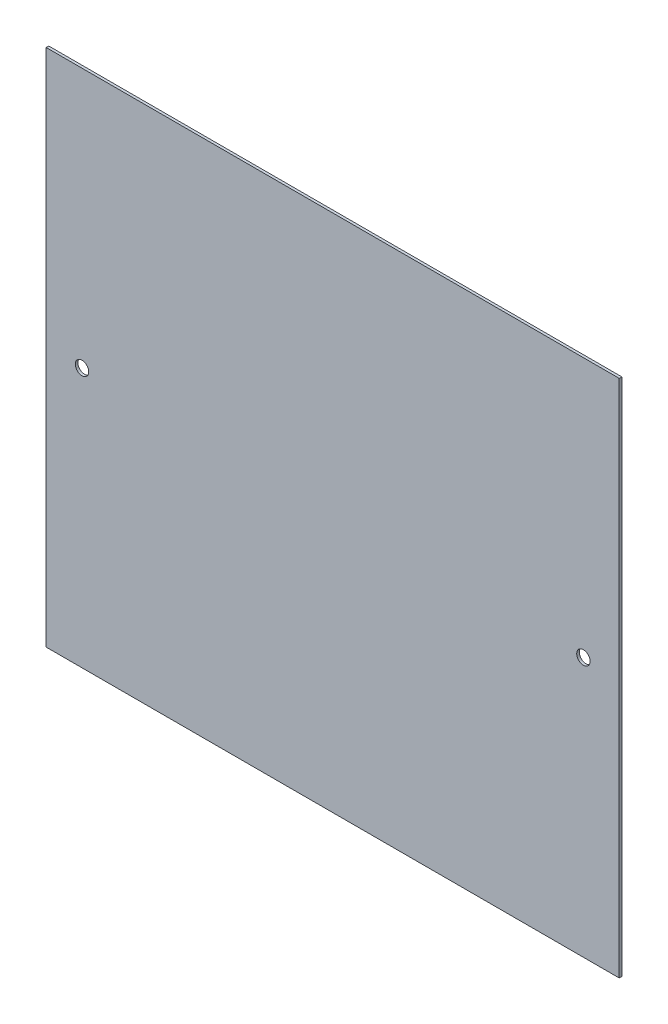
SolidWorks part; units mm, degrees
material "Alumina"
ref_plane "Front Plane" through (0, 0, 0) normal (0, 0, 1) x (1, 0, 0)
ref_plane "Top Plane" through (0, 0, 0) normal (0, 1, 0) x (1, 0, 0)
ref_plane "Right Plane" through (0, 0, 0) normal (1, 0, 0) x (0, 0, -1)
sketch "Sketch2" plane through (0, 0, 0) normal (0, 0, 1) x (1, 0, 0)
  line L1 (-144, 130.5) -> (144, 130.5)
  line L2 (-144, 130.5) -> (-144, -130.5)
  line L3 (-144, -130.5) -> (144, -130.5)
  line L4 (144, 130.5) -> (144, -130.5)
  line L5 (-144, 130.5) -> (144, -130.5) construction
  line L6 (-144, -130.5) -> (144, 130.5) construction
  point P0 (0, 0)
  dimension "D1" = 288
  dimension "D2" = 261
extrude "Boss-Extrude1" add sketch "Sketch2" along normal blind 1.2954
hole_wizard "1/4 Clearance Hole1" positions "Sketch3" profile "Sketch4" hole size "1/4" standard "ANSI Inch" end condition through all
sketch "Sketch3" plane through (0, 0, 1.2954) normal (0, 0, 1) x (1, 0, 0)
  line L0 (-144, 130.5) -> (-144, -130.5) construction
  line L1 (144, -130.5) -> (144, 130.5) construction
  point P0 (-126, 0)
  point P2 (126, 0)
  point P5 (0, 0)
  dimension "D1" = 18
  dimension "D2" = 18
sketch "Sketch4" plane through (-126, 0, 1.2954) normal (1, 0, 0) x (0, -1, 0)
  line L0 (0, 0) -> (0, 1.2954)
  line L1 (0, 1.2954) -> (3.3782, 1.2954)
  line L2 (3.3782, 1.2954) -> (3.3782, 0)
  line L5 (3.3782, 0) -> (0, 0)
  line L11 (0, -6.35) -> (0, 107.95) construction
  dimension "Thru Hole Dia." = 6.7564
  dimension "Thru Hole Depth" = 1.2954
